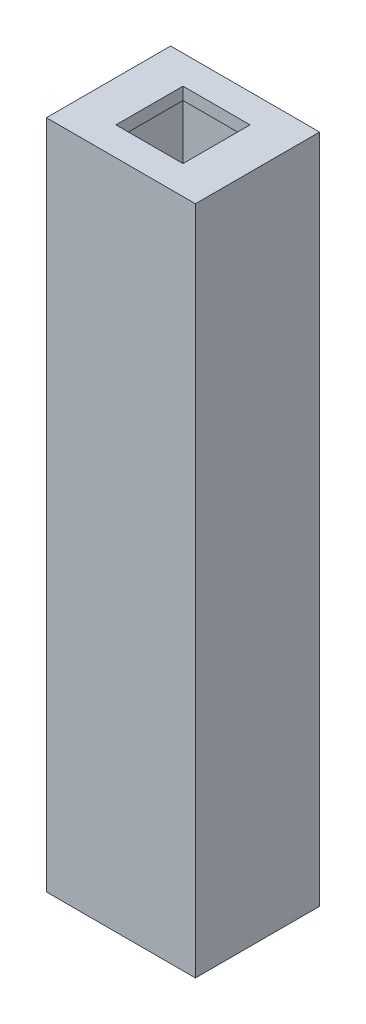
SolidWorks part; units mm, degrees
ref_plane "前视基准面" through (0, 0, 0) normal (0, 0, 1) x (1, 0, 0)
ref_plane "上视基准面" through (0, 0, 0) normal (0, 1, 0) x (1, 0, 0)
ref_plane "右视基准面" through (0, 0, 0) normal (1, 0, 0) x (0, 0, -1)
other "Configuration Table"
sketch "草图1" plane through (0, 0, 0) normal (0, 1, 0) x (1, 0, 0)
  line L1 (-3.1, 3.1) -> (3.1, 3.1)
  line L2 (-3.1, 3.1) -> (-3.1, -3.1)
  line L3 (-3.1, -3.1) -> (3.1, -3.1)
  line L4 (3.1, 3.1) -> (3.1, -3.1)
  line L5 (-3.1, 3.1) -> (3.1, -3.1) construction
  line L6 (-3.1, -3.1) -> (3.1, 3.1) construction
  line L7 (-6, 5) -> (6, 5)
  line L8 (-6, 5) -> (-6, -5)
  line L9 (-6, -5) -> (6, -5)
  line L10 (6, 5) -> (6, -5)
  line L11 (-6, 5) -> (6, -5) construction
  line L12 (-6, -5) -> (6, 5) construction
  line L13 (-2.7, -2.7) -> (2.7, -2.7)
  line L14 (-2.7, -2.7) -> (-2.7, 2.7)
  line L15 (-2.7, 2.7) -> (2.7, 2.7)
  line L16 (2.7, -2.7) -> (2.7, 2.7)
  line L17 (-2.7, -2.7) -> (2.7, 2.7) construction
  line L18 (-2.7, 2.7) -> (2.7, -2.7) construction
  point P0 (0, 0)
  point P5 (0, 0)
  point P13 (0, 0)
  dimension "D1" = 6.2
  dimension "D2" = 10
  dimension "D3" = 5.4
  dimension "D4" = 12
extrude "凸台-拉伸1" add sketch "草图1" along normal blind 54 contours L10 L7 L8 L9 L1 L4 L3 L2 region at (0, 0, -4.8438)
extrude "凸台-拉伸2" add sketch "草图1<3>" against normal blind 1 from surface contours L10 L7 L8 L9 L1 L4 L3 L2 | L4 L1 L2 L3 L16 L13 L14 L15 region at (0, 0, -3.0123) region at (0, 0, -4.8438) starting at face at (0, 54, 0)
sketch "草图1<3>" plane through (0, 0, 0) normal (0, 1, 0) x (1, 0, 0) same geometry as "草图1"
sketch "草图2" plane through (0, 0, 0) normal (0, -1, 0) x (1, 0, 0)
  line L0 (-6, -5) -> (-6, 5) construction
  line L1 (-3, -3) -> (3, -3)
  line L2 (-3, -3) -> (-3, 3)
  line L3 (-3, 3) -> (3, 3)
  line L4 (3, -3) -> (3, 3)
  line L5 (-3, -3) -> (3, 3) construction
  line L6 (-3, 3) -> (3, -3) construction
  line L8 (-6, 5) -> (6, 5) construction
  line L9 (-6, -5) -> (6, -5) construction
  line L10 (6, -5) -> (6, 5) construction
  circle A0 centre (-4.5, 3.5) radius 0.3
  circle A1 centre (4.5, -3.5) radius 0.3
  circle A2 centre (4.5, 3.5) radius 0.3
  circle A3 centre (-4.5, -3.5) radius 0.3
  point P0 (0, 0)
  point P20 (-6.886, 6.783)
  dimension "D2" = 0.6
  dimension "D1" = 6
  dimension "D3" = 1.5
  dimension "D4" = 1.5
  dimension "D5" = 1.5
  dimension "D6" = 1.5
extrude "切除-拉伸1" cut sketch "草图2" against normal blind 2 contours A0 | A2 | A3 | A1
